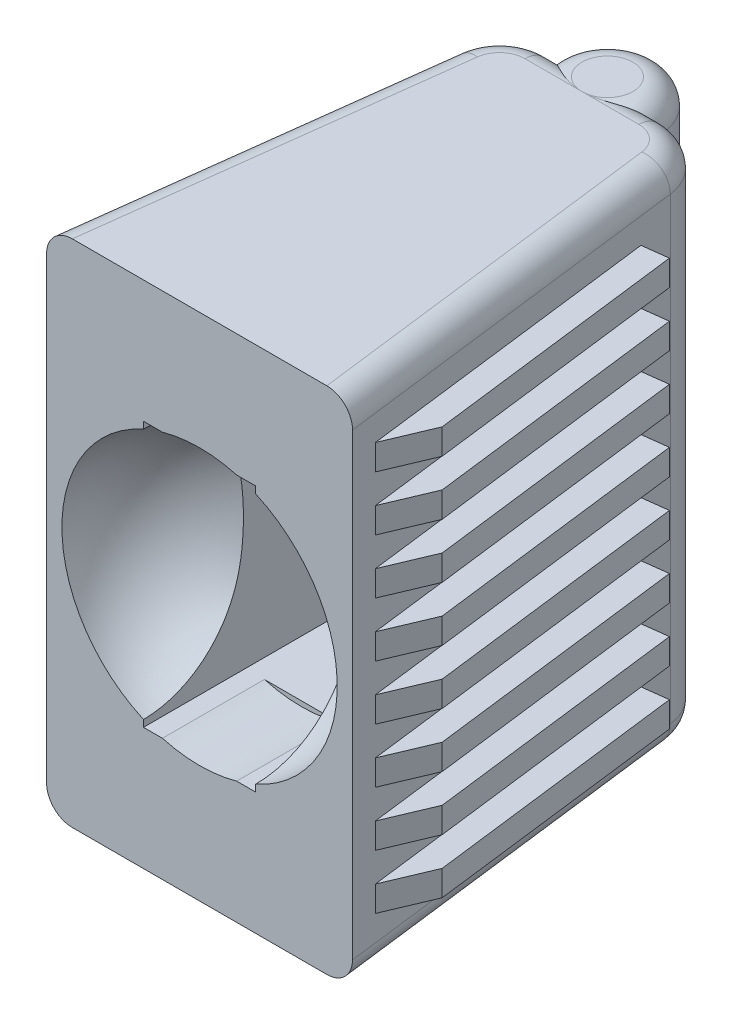
SolidWorks part; units mm, degrees
ref_plane "Спереди" through (0, 0, 0) normal (0, 0, 1) x (1, 0, 0)
ref_plane "Сверху" through (0, 0, 0) normal (0, 1, 0) x (1, 0, 0)
ref_plane "Справа" through (0, 0, 0) normal (1, 0, 0) x (0, 0, -1)
sketch "Sketch1" plane through (0, 0, 0) normal (0, 1, 0) x (1, 0, 0)
  line L0 (3, 0) -> (-3, 0)
  line L1 (-3, 0) -> (-2, 8)
  line L2 (-2, 8) -> (2, 8) construction
  line L3 (2, 8) -> (3, 0)
  line L4 (2, 8) -> (1, 8)
  line L5 (0, 8) -> (0, 0) construction
  line L6 (-1, 8) -> (-2, 8)
  arc A0 (1, 8) -> (-1, 8) centre (0, 8) ccw
  point P4 (0, 0)
  point P8 (0, 8)
  dimension "D4" = 1
  dimension "D1" = 8
  dimension "D2" = 6
  dimension "D3" = 4
extrude "Boss-Extrude1" add sketch "Sketch1" along normal blind 10
sketch "Sketch2" plane through (0, 0, 0) normal (0, 0, 1) x (1, 0, 0)
  line L0 (0, 10) -> (0, 0) construction
  line L1 (-3, 10) -> (3, 10) construction
  circle A0 centre (0, 5) radius 2.7
  dimension "D1" = 5.4
extrude "Cut-Extrude1" cut sketch "Sketch2" against normal blind 2
fillet "Fillet1" radius 1 2 edges at (-2, 5, -8) (2, 5, -8)
sketch "Sketch3" plane through (0, 0, 0) normal (0, 0, 1) x (1, 0, 0)
  line L0 (0, 2.3) -> (0, 7.7) construction
  line L2 (1.1, 2.4) -> (-1.1, 2.4)
  line L3 (1.1, 2.4) -> (1.1, 7.6)
  line L4 (1.1, 7.6) -> (-1.1, 7.6)
  line L5 (-1.1, 2.4) -> (-1.1, 7.6)
  line L6 (1.1, 2.4) -> (-1.1, 7.6) construction
  line L7 (1.1, 7.6) -> (-1.1, 2.4) construction
  circle A0 centre (0, 5) radius 2.7 construction
  point P5 (0, 5)
  dimension "D1" = 5.2
  dimension "D2" = 2.2
extrude "Cut-Extrude2" cut sketch "Sketch3" against normal blind 6
sketch "Sketch4" plane through (-2.9538, 0, -0.3692) normal (-0.9923, 0, -0.124) x (-0.124, 0, 0.9923)
  line L0 (-6.8074, 5) -> (0.3721, 5) construction
  line L1 (-6.8074, 10) -> (-6.8074, 0) construction
  line L2 (0.3721, 10) -> (0.3721, 0) construction
  line L3 (-6.1442, 1.25) -> (-1.1442, 1.25) construction
  line L4 (-1.1442, 9) -> (-6.1442, 9) construction
  line L5 (-1.1442, 9) -> (-1.1442, 1) construction
  line L6 (-1.1442, 1) -> (-6.1442, 1) construction
  line L7 (-6.1442, 9) -> (-6.1442, 1) construction
  line L8 (-1.1442, 9) -> (-6.1442, 1) construction
  line L9 (-1.1442, 1) -> (-6.1442, 9) construction
  line L10 (-1.1442, 2.0714) -> (-6.1442, 2.0714)
  line L11 (-1.1442, 1.5) -> (-6.1442, 1.5)
  line L12 (-1.1442, 1.5) -> (-1.1442, 1)
  line L13 (-1.1442, 1) -> (-6.1442, 1)
  line L14 (-6.1442, 1.5) -> (-6.1442, 1)
  line L15 (-1.1442, 1.5) -> (-6.1442, 1) construction
  line L16 (-1.1442, 1) -> (-6.1442, 1.5) construction
  line L17 (-6.1442, 2.5714) -> (-6.1442, 2.0714)
  line L18 (-1.1442, 2.5714) -> (-6.1442, 2.5714)
  line L19 (-1.1442, 2.5714) -> (-1.1442, 2.0714)
  line L20 (-1.1442, 3.1429) -> (-6.1442, 3.1429)
  line L21 (-6.1442, 3.6429) -> (-6.1442, 3.1429)
  line L22 (-1.1442, 3.6429) -> (-6.1442, 3.6429)
  line L23 (-1.1442, 3.6429) -> (-1.1442, 3.1429)
  line L24 (-1.1442, 4.2143) -> (-6.1442, 4.2143)
  line L25 (-6.1442, 4.7143) -> (-6.1442, 4.2143)
  line L26 (-1.1442, 4.7143) -> (-6.1442, 4.7143)
  line L27 (-1.1442, 4.7143) -> (-1.1442, 4.2143)
  line L28 (-1.1442, 5.2857) -> (-6.1442, 5.2857)
  line L29 (-6.1442, 5.7857) -> (-6.1442, 5.2857)
  line L30 (-1.1442, 5.7857) -> (-6.1442, 5.7857)
  line L31 (-1.1442, 5.7857) -> (-1.1442, 5.2857)
  line L32 (-1.1442, 6.3571) -> (-6.1442, 6.3571)
  line L33 (-6.1442, 6.8571) -> (-6.1442, 6.3571)
  line L34 (-1.1442, 6.8571) -> (-6.1442, 6.8571)
  line L35 (-1.1442, 6.8571) -> (-1.1442, 6.3571)
  line L36 (-1.1442, 7.4286) -> (-6.1442, 7.4286)
  line L37 (-6.1442, 7.9286) -> (-6.1442, 7.4286)
  line L38 (-1.1442, 7.9286) -> (-6.1442, 7.9286)
  line L39 (-1.1442, 7.9286) -> (-1.1442, 7.4286)
  line L40 (-1.1442, 8.5) -> (-6.1442, 8.5)
  line L41 (-6.1442, 9) -> (-6.1442, 8.5)
  line L42 (-1.1442, 9) -> (-6.1442, 9)
  line L43 (-1.1442, 9) -> (-1.1442, 8.5)
  point P6 (-3.6442, 5)
  point P13 (-3.6442, 1.25)
  dimension "D1" = 8
  dimension "D2" = 5
  dimension "D3" = 0.5
  dimension "D4" = 8
extrude "Boss-Extrude2" add sketch "Sketch4" along normal blind 0.5
mirror "Mirror1" about plane through (0, 0, 0) normal (1, 0, 0) of "Boss-Extrude2"
chamfer "Chamfer1" distance 1 angle 30 16 edges at (2.8119, 1.25, -1.5046) (2.8119, 2.3214, -1.5046) (2.8119, 3.3929, -1.5046) (2.8119, 4.4643, -1.5046) (2.8119, 5.5357, -1.5046) (2.8119, 6.6071, -1.5046) (2.8119, 7.6786, -1.5046) (2.8119, 8.75, -1.5046) (-2.8119, 1.25, -1.5046) (-2.8119, 2.3214, -1.5046) (-2.8119, 3.3929, -1.5046) (-2.8119, 4.4643, -1.5046) (-2.8119, 5.5357, -1.5046) (-2.8119, 6.6071, -1.5046) (-2.8119, 8.75, -1.5046) (-2.8119, 7.6786, -1.5046)
fillet "Fillet2" radius 0.5 14 edges at (1.0586, 10, -8) (1.779, 10, -7.7497) (-1.0586, 10, -8) (-1.779, 10, -7.7497) (1.0586, 0, -8) (1.779, 0, -7.7497) (-1.0586, 0, -8) (-1.779, 0, -7.7497) (0, 0, -9) (0, 10, -9) (2.5547, 10, -3.562) (-2.5547, 10, -3.562) (2.5547, 0, -3.562) (-2.5547, 0, -3.562)
fillet "Fillet3" radius 2 2 edges at (2.7, 5, -2) (-2.7, 5, -2)
